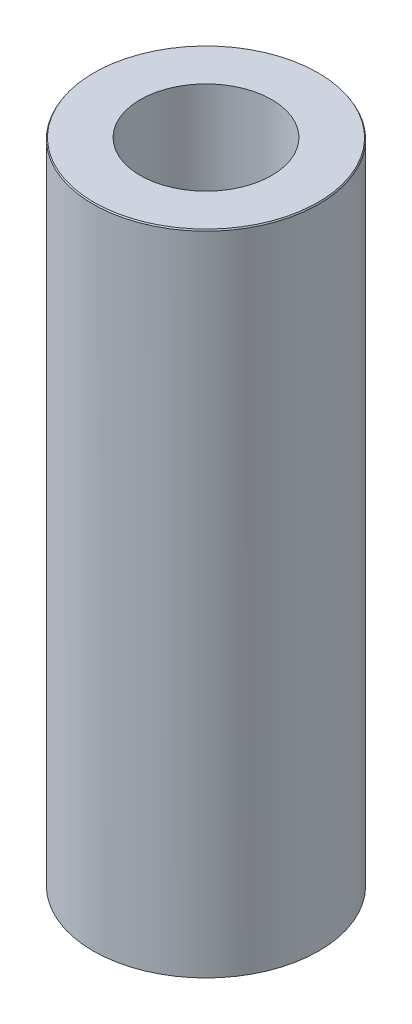
SolidWorks part; units mm, degrees
ref_plane "Front Plane" through (0, 0, 0) normal (0, 0, 1) x (1, 0, 0)
ref_plane "Top Plane" through (0, 0, 0) normal (0, 1, 0) x (1, 0, 0)
ref_plane "Right Plane" through (0, 0, 0) normal (1, 0, 0) x (0, 0, -1)
sketch "Sketch1" plane through (0, 0, 0) normal (0, 1, 0) x (1, 0, 0)
  circle A0 centre (0, 0) radius 42.5
  dimension "SHAFT_OD" = 85
extrude "Boss-Extrude1" add sketch "Sketch1" along normal blind 244.2455
sketch "Sketch2" plane through (0, 0, 0) normal (0, 1, 0) x (1, 0, 0)
  circle A0 centre (0, 0) radius 24.7524
  dimension "BORE_D" = 49.5049
extrude "Cut-Extrude1" cut sketch "Sketch2" along normal through all
chamfer "Chamfer1" distance 0.4893 angle 30 2 edges at (0, 244.2455, 42.5) (0, 0, 42.5) first distance on face at (0, 244.2455, 42.5) first distance on face at (0, 0, 24.7524)
